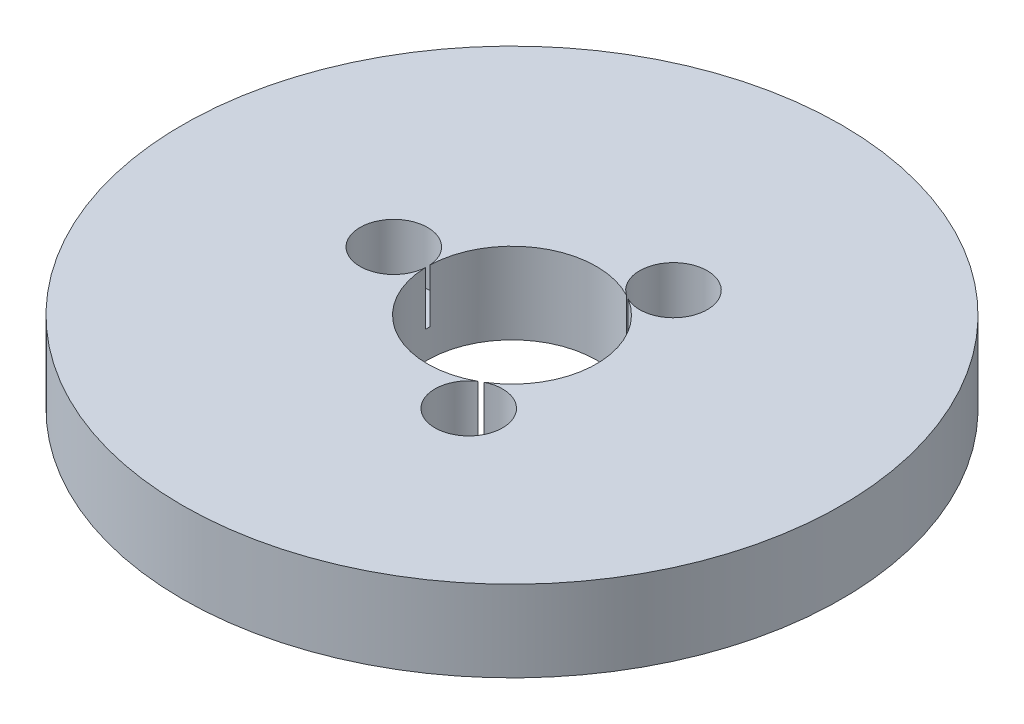
SolidWorks part; units mm, degrees
ref_plane "Front Plane" through (0, 0, 0) normal (0, 0, 1) x (1, 0, 0)
ref_plane "Top Plane" through (0, 0, 0) normal (0, 1, 0) x (1, 0, 0)
ref_plane "Right Plane" through (0, 0, 0) normal (1, 0, 0) x (0, 0, -1)
sketch "Sketch1" plane through (0, 0, 0) normal (0, 1, 0) x (1, 0, 0)
  circle A0 centre (0, 0) radius 97.5
  dimension "FLANGE_OD" = 195
extrude "Boss-Extrude1" add sketch "Sketch1" along normal blind 24
sketch "Sketch2" plane through (0, 0, 0) normal (0, 1, 0) x (1, 0, 0)
  circle A0 centre (0, 0) radius 25
  dimension "BORE_D" = 50
extrude "Cut-Extrude1" cut sketch "Sketch2" along normal through all
sketch "Sketch3" plane through (0, 24, 0) normal (0, 1, 0) x (1, 0, 0)
  circle A0 centre (0, 0) radius 34.9692 construction
  circle A1 centre (-34.9692, 0) radius 10
  dimension "BOLT_D" = 20
  dimension "BOLT_PCD" = 69.9385
extrude "Cut-Extrude2" cut sketch "Sketch3" against normal blind 15.8238
pattern_circular "CirPattern1" count 3 over 360 about axis through (0, 0, 0) along (0, 1, 0) of "Cut-Extrude2"
